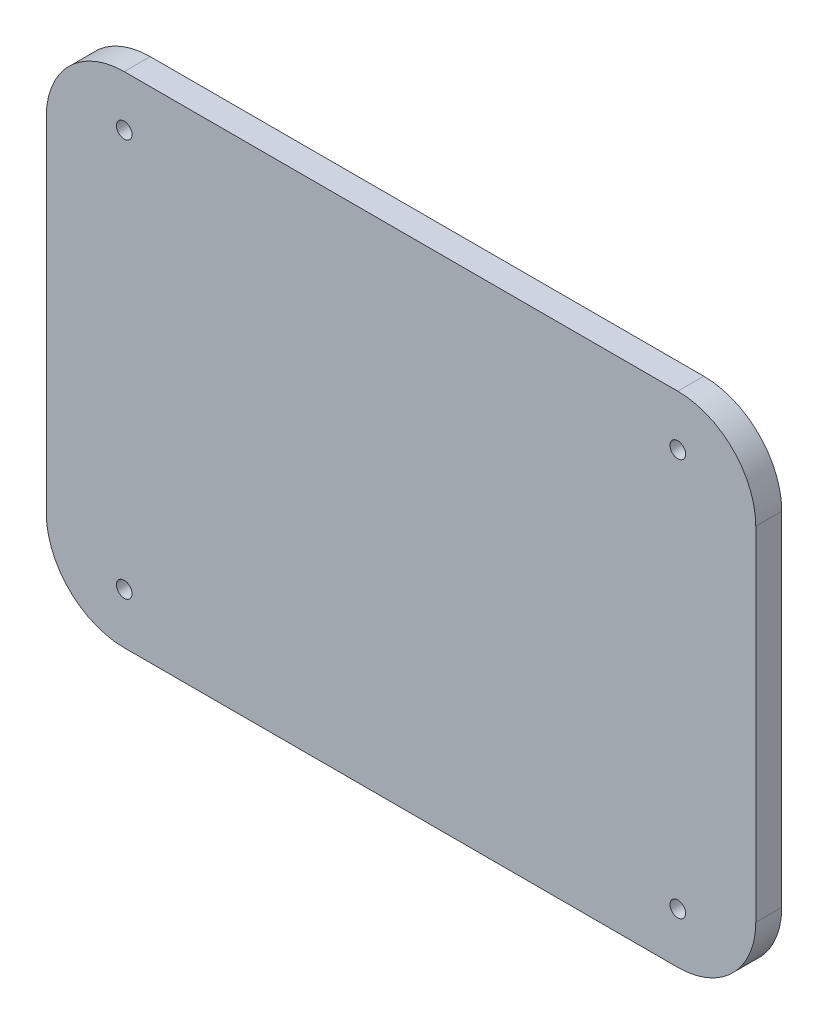
SolidWorks part; units mm, degrees
material "Acrylic (Medium-high impact)"
ref_plane "Front Plane" through (0, 0, 0) normal (0, 0, 1) x (1, 0, 0)
ref_plane "Top Plane" through (0, 0, 0) normal (0, 1, 0) x (1, 0, 0)
ref_plane "Right Plane" through (0, 0, 0) normal (1, 0, 0) x (0, 0, -1)
sketch "Model" plane through (0, 0, 0) normal (0, 0, 1) x (1, 0, 0)
  line L0 (836.1886, 1132.0702) -> (835.7887, 1132.0702)
  line L1 (836.1886, 1132.0702) -> (835.7887, 1132.0702)
  line L2 (836.5018, 1132.0643) -> (836.1886, 1132.0702)
  line L3 (836.5018, 1132.0643) -> (836.1886, 1132.0702)
  line L4 (836.7677, 1132.0446) -> (836.5018, 1132.0643)
  line L5 (836.7677, 1132.0446) -> (836.5018, 1132.0643)
  line L6 (836.9883, 1132.0111) -> (836.7677, 1132.0446)
  line L7 (836.9883, 1132.0111) -> (836.7677, 1132.0446)
  line L8 (837.1636, 1131.9638) -> (836.9883, 1132.0111)
  line L9 (837.1636, 1131.9638) -> (836.9883, 1132.0111)
  line L10 (837.3133, 1131.9008) -> (837.1636, 1131.9638)
  line L11 (837.3133, 1131.9008) -> (837.1636, 1131.9638)
  line L12 (837.4611, 1131.8141) -> (837.3133, 1131.9008)
  line L13 (837.4611, 1131.8141) -> (837.3133, 1131.9008)
  line L14 (837.6029, 1131.7077) -> (837.4611, 1131.8141)
  line L15 (837.6029, 1131.7077) -> (837.4611, 1131.8141)
  line L16 (837.7408, 1131.5777) -> (837.6029, 1131.7077)
  line L17 (837.7408, 1131.5777) -> (837.6029, 1131.7077)
  line L18 (837.8156, 1131.495) -> (837.7408, 1131.5777)
  line L19 (837.8156, 1131.495) -> (837.7408, 1131.5777)
  line L20 (837.9082, 1131.3847) -> (837.8156, 1131.495)
  line L21 (837.9082, 1131.3847) -> (837.8156, 1131.495)
  line L22 (838.0146, 1131.2468) -> (837.9082, 1131.3847)
  line L23 (838.0146, 1131.2468) -> (837.9082, 1131.3847)
  line L24 (838.1367, 1131.0833) -> (838.0146, 1131.2468)
  line L25 (838.1367, 1131.0833) -> (838.0146, 1131.2468)
  line L26 (838.2746, 1130.8903) -> (838.1367, 1131.0833)
  line L27 (838.2746, 1130.8903) -> (838.1367, 1131.0833)
  line L28 (838.4262, 1130.6716) -> (838.2746, 1130.8903)
  line L29 (838.4262, 1130.6716) -> (838.2746, 1130.8903)
  line L30 (838.5956, 1130.4254) -> (838.4262, 1130.6716)
  line L31 (838.5956, 1130.4254) -> (838.4262, 1130.6716)
  line L32 (838.7788, 1130.1516) -> (838.5956, 1130.4254)
  line L33 (838.7788, 1130.1516) -> (838.5956, 1130.4254)
  line L34 (840.1971, 1128.0361) -> (838.7788, 1130.1516)
  line L35 (840.1971, 1128.0361) -> (838.7788, 1130.1516)
  line L36 (842.5963, 1128.0361) -> (840.1971, 1128.0361)
  line L37 (842.5963, 1128.0361) -> (840.1971, 1128.0361)
  line L38 (841.4104, 1129.9369) -> (842.5963, 1128.0361)
  line L39 (841.4104, 1129.9369) -> (842.5963, 1128.0361)
  line L40 (841.2371, 1130.2127) -> (841.4104, 1129.9369)
  line L41 (841.2371, 1130.2127) -> (841.4104, 1129.9369)
  line L42 (841.0716, 1130.4648) -> (841.2371, 1130.2127)
  line L43 (841.0716, 1130.4648) -> (841.2371, 1130.2127)
  line L44 (840.916, 1130.6953) -> (841.0716, 1130.4648)
  line L45 (840.916, 1130.6953) -> (841.0716, 1130.4648)
  line L46 (840.7703, 1130.9041) -> (840.916, 1130.6953)
  line L47 (840.7703, 1130.9041) -> (840.916, 1130.6953)
  line L48 (840.6324, 1131.0892) -> (840.7703, 1130.9041)
  line L49 (840.6324, 1131.0892) -> (840.7703, 1130.9041)
  line L50 (840.5044, 1131.2527) -> (840.6324, 1131.0892)
  line L51 (840.5044, 1131.2527) -> (840.6324, 1131.0892)
  line L52 (840.3862, 1131.3945) -> (840.5044, 1131.2527)
  line L53 (840.3862, 1131.3945) -> (840.5044, 1131.2527)
  line L54 (840.2759, 1131.5147) -> (840.3862, 1131.3945)
  line L55 (840.2759, 1131.5147) -> (840.3862, 1131.3945)
  line L56 (840.0513, 1131.7274) -> (840.2759, 1131.5147)
  line L57 (840.0513, 1131.7274) -> (840.2759, 1131.5147)
  line L58 (839.8011, 1131.9323) -> (840.0513, 1131.7274)
  line L59 (839.8011, 1131.9323) -> (840.0513, 1131.7274)
  line L60 (839.5214, 1132.1273) -> (839.8011, 1131.9323)
  line L61 (839.5214, 1132.1273) -> (839.8011, 1131.9323)
  line L62 (839.2142, 1132.3144) -> (839.5214, 1132.1273)
  line L63 (839.2142, 1132.3144) -> (839.5214, 1132.1273)
  line L64 (839.5195, 1132.3676) -> (839.2142, 1132.3144)
  line L65 (839.5195, 1132.3676) -> (839.2142, 1132.3144)
  line L66 (839.8071, 1132.4365) -> (839.5195, 1132.3676)
  line L67 (839.8071, 1132.4365) -> (839.5195, 1132.3676)
  line L68 (840.0769, 1132.5212) -> (839.8071, 1132.4365)
  line L69 (840.0769, 1132.5212) -> (839.8071, 1132.4365)
  line L70 (840.329, 1132.6237) -> (840.0769, 1132.5212)
  line L71 (840.329, 1132.6237) -> (840.0769, 1132.5212)
  line L72 (840.5634, 1132.7399) -> (840.329, 1132.6237)
  line L73 (840.5634, 1132.7399) -> (840.329, 1132.6237)
  line L74 (840.7782, 1132.8738) -> (840.5634, 1132.7399)
  line L75 (840.7782, 1132.8738) -> (840.5634, 1132.7399)
  line L76 (840.9771, 1133.0235) -> (840.7782, 1132.8738)
  line L77 (840.9771, 1133.0235) -> (840.7782, 1132.8738)
  line L78 (841.1563, 1133.189) -> (840.9771, 1133.0235)
  line L79 (841.1563, 1133.189) -> (840.9771, 1133.0235)
  line L80 (841.3159, 1133.3702) -> (841.1563, 1133.189)
  line L81 (841.3159, 1133.3702) -> (841.1563, 1133.189)
  line L82 (841.4558, 1133.5652) -> (841.3159, 1133.3702)
  line L83 (841.4558, 1133.5652) -> (841.3159, 1133.3702)
  line L84 (841.572, 1133.774) -> (841.4558, 1133.5652)
  line L85 (841.572, 1133.774) -> (841.4558, 1133.5652)
  line L86 (841.6685, 1133.9966) -> (841.572, 1133.774)
  line L87 (841.6685, 1133.9966) -> (841.572, 1133.774)
  line L88 (841.7433, 1134.233) -> (841.6685, 1133.9966)
  line L89 (841.7433, 1134.233) -> (841.6685, 1133.9966)
  line L90 (841.7965, 1134.4831) -> (841.7433, 1134.233)
  line L91 (841.7965, 1134.4831) -> (841.7433, 1134.233)
  line L92 (841.83, 1134.7471) -> (841.7965, 1134.4831)
  line L93 (841.83, 1134.7471) -> (841.7965, 1134.4831)
  line L94 (841.8399, 1135.0248) -> (841.83, 1134.7471)
  line L95 (841.8399, 1135.0248) -> (841.83, 1134.7471)
  line L96 (841.832, 1135.2454) -> (841.8399, 1135.0248)
  line L97 (841.832, 1135.2454) -> (841.8399, 1135.0248)
  line L98 (841.8123, 1135.4601) -> (841.832, 1135.2454)
  line L99 (841.8123, 1135.4601) -> (841.832, 1135.2454)
  line L100 (841.7768, 1135.665) -> (841.8123, 1135.4601)
  line L101 (841.7768, 1135.665) -> (841.8123, 1135.4601)
  line L102 (841.7296, 1135.8639) -> (841.7768, 1135.665)
  line L103 (841.7296, 1135.8639) -> (841.7768, 1135.665)
  line L104 (841.6665, 1136.053) -> (841.7296, 1135.8639)
  line L105 (841.6665, 1136.053) -> (841.7296, 1135.8639)
  line L106 (841.5897, 1136.2343) -> (841.6665, 1136.053)
  line L107 (841.5897, 1136.2343) -> (841.6665, 1136.053)
  line L108 (841.5011, 1136.4076) -> (841.5897, 1136.2343)
  line L109 (841.5011, 1136.4076) -> (841.5897, 1136.2343)
  line L110 (841.3967, 1136.5731) -> (841.5011, 1136.4076)
  line L111 (841.3967, 1136.5731) -> (841.5011, 1136.4076)
  line L112 (841.1603, 1136.8725) -> (841.3967, 1136.5731)
  line L113 (841.1603, 1136.8725) -> (841.3967, 1136.5731)
  line L114 (840.8924, 1137.1226) -> (841.1603, 1136.8725)
  line L115 (840.8924, 1137.1226) -> (841.1603, 1136.8725)
  line L116 (840.593, 1137.3255) -> (840.8924, 1137.1226)
  line L117 (840.593, 1137.3255) -> (840.8924, 1137.1226)
  line L118 (840.264, 1137.4811) -> (840.593, 1137.3255)
  line L119 (840.264, 1137.4811) -> (840.593, 1137.3255)
  line L120 (840.0769, 1137.5422) -> (840.264, 1137.4811)
  line L121 (840.0769, 1137.5422) -> (840.264, 1137.4811)
  line L122 (839.8622, 1137.5954) -> (840.0769, 1137.5422)
  line L123 (839.8622, 1137.5954) -> (840.0769, 1137.5422)
  line L124 (839.618, 1137.6407) -> (839.8622, 1137.5954)
  line L125 (839.618, 1137.6407) -> (839.8622, 1137.5954)
  line L126 (839.3442, 1137.6781) -> (839.618, 1137.6407)
  line L127 (839.3442, 1137.6781) -> (839.618, 1137.6407)
  line L128 (839.0428, 1137.7057) -> (839.3442, 1137.6781)
  line L129 (839.0428, 1137.7057) -> (839.3442, 1137.6781)
  line L130 (838.7119, 1137.7274) -> (839.0428, 1137.7057)
  line L131 (838.7119, 1137.7274) -> (839.0428, 1137.7057)
  line L132 (838.3534, 1137.7392) -> (838.7119, 1137.7274)
  line L133 (838.3534, 1137.7392) -> (838.7119, 1137.7274)
  line L134 (837.9653, 1137.7431) -> (838.3534, 1137.7392)
  line L135 (837.9653, 1137.7431) -> (838.3534, 1137.7392)
  line L136 (833.7717, 1137.7431) -> (837.9653, 1137.7431)
  line L137 (833.7717, 1137.7431) -> (837.9653, 1137.7431)
  line L138 (833.7717, 1128.0361) -> (833.7717, 1137.7431)
  line L139 (833.7717, 1128.0361) -> (833.7717, 1137.7431)
  line L140 (835.7887, 1128.0361) -> (833.7717, 1128.0361)
  line L141 (835.7887, 1128.0361) -> (833.7717, 1128.0361)
  line L142 (835.7887, 1132.0702) -> (835.7887, 1128.0361)
  line L143 (835.7887, 1132.0702) -> (835.7887, 1128.0361)
  line L144 (851.3546, 1130.1792) -> (847.4801, 1130.1792)
  line L145 (851.3546, 1130.1792) -> (847.4801, 1130.1792)
  line L146 (852.1406, 1128.0361) -> (851.3546, 1130.1792)
  line L147 (852.1406, 1128.0361) -> (851.3546, 1130.1792)
  line L148 (854.396, 1128.0361) -> (852.1406, 1128.0361)
  line L149 (854.396, 1128.0361) -> (852.1406, 1128.0361)
  line L150 (850.6948, 1137.7431) -> (854.396, 1128.0361)
  line L151 (850.6948, 1137.7431) -> (854.396, 1128.0361)
  line L152 (848.138, 1137.7431) -> (850.6948, 1137.7431)
  line L153 (848.138, 1137.7431) -> (850.6948, 1137.7431)
  line L154 (844.4368, 1128.0361) -> (848.138, 1137.7431)
  line L155 (844.4368, 1128.0361) -> (848.138, 1137.7431)
  line L156 (846.6922, 1128.0361) -> (844.4368, 1128.0361)
  line L157 (846.6922, 1128.0361) -> (844.4368, 1128.0361)
  line L158 (847.4801, 1130.1792) -> (846.6922, 1128.0361)
  line L159 (847.4801, 1130.1792) -> (846.6922, 1128.0361)
  line L160 (850.4446, 1044.1431) -> (850.4446, 1039.1431)
  line L161 (850.4446, 1044.1431) -> (850.4446, 1039.1431)
  line L162 (825.4446, 1044.1431) -> (850.4446, 1044.1431)
  line L163 (825.4446, 1044.1431) -> (850.4446, 1044.1431)
  line L164 (825.4446, 1039.1431) -> (825.4446, 1044.1431)
  line L165 (825.4446, 1039.1431) -> (825.4446, 1044.1431)
  line L166 (850.4446, 1039.1431) -> (825.4446, 1039.1431)
  line L167 (850.4446, 1039.1431) -> (825.4446, 1039.1431)
  line L168 (822.752, 1129.8246) -> (822.6141, 1130.1575)
  line L169 (822.752, 1129.8246) -> (822.6141, 1130.1575)
  line L170 (822.9155, 1129.5193) -> (822.752, 1129.8246)
  line L171 (822.9155, 1129.5193) -> (822.752, 1129.8246)
  line L172 (823.1026, 1129.2396) -> (822.9155, 1129.5193)
  line L173 (823.1026, 1129.2396) -> (822.9155, 1129.5193)
  line L174 (823.3153, 1128.9875) -> (823.1026, 1129.2396)
  line L175 (823.3153, 1128.9875) -> (823.1026, 1129.2396)
  line L176 (823.5537, 1128.761) -> (823.3153, 1128.9875)
  line L177 (823.5537, 1128.761) -> (823.3153, 1128.9875)
  line L178 (823.8157, 1128.562) -> (823.5537, 1128.761)
  line L179 (823.8157, 1128.562) -> (823.5537, 1128.761)
  line L180 (824.1033, 1128.3887) -> (823.8157, 1128.562)
  line L181 (824.1033, 1128.3887) -> (823.8157, 1128.562)
  line L182 (824.4145, 1128.2429) -> (824.1033, 1128.3887)
  line L183 (824.4145, 1128.2429) -> (824.1033, 1128.3887)
  line L184 (824.7513, 1128.1227) -> (824.4145, 1128.2429)
  line L185 (824.7513, 1128.1227) -> (824.4145, 1128.2429)
  line L186 (825.1137, 1128.0302) -> (824.7513, 1128.1227)
  line L187 (825.1137, 1128.0302) -> (824.7513, 1128.1227)
  line L188 (825.4998, 1127.9632) -> (825.1137, 1128.0302)
  line L189 (825.4998, 1127.9632) -> (825.1137, 1128.0302)
  line L190 (825.9115, 1127.9238) -> (825.4998, 1127.9632)
  line L191 (825.9115, 1127.9238) -> (825.4998, 1127.9632)
  line L192 (826.3488, 1127.91) -> (825.9115, 1127.9238)
  line L193 (826.3488, 1127.91) -> (825.9115, 1127.9238)
  line L194 (826.8393, 1127.9238) -> (826.3488, 1127.91)
  line L195 (826.8393, 1127.9238) -> (826.3488, 1127.91)
  line L196 (827.2982, 1127.9632) -> (826.8393, 1127.9238)
  line L197 (827.2982, 1127.9632) -> (826.8393, 1127.9238)
  line L198 (827.7217, 1128.0282) -> (827.2982, 1127.9632)
  line L199 (827.7217, 1128.0282) -> (827.2982, 1127.9632)
  line L200 (828.1117, 1128.1208) -> (827.7217, 1128.0282)
  line L201 (828.1117, 1128.1208) -> (827.7217, 1128.0282)
  line L202 (828.4683, 1128.239) -> (828.1117, 1128.1208)
  line L203 (828.4683, 1128.239) -> (828.1117, 1128.1208)
  line L204 (828.7913, 1128.3847) -> (828.4683, 1128.239)
  line L205 (828.7913, 1128.3847) -> (828.4683, 1128.239)
  line L206 (829.0809, 1128.5561) -> (828.7913, 1128.3847)
  line L207 (829.0809, 1128.5561) -> (828.7913, 1128.3847)
  line L208 (829.3369, 1128.7531) -> (829.0809, 1128.5561)
  line L209 (829.3369, 1128.7531) -> (829.0809, 1128.5561)
  line L210 (829.5615, 1128.9698) -> (829.3369, 1128.7531)
  line L211 (829.5615, 1128.9698) -> (829.3369, 1128.7531)
  line L212 (829.7545, 1129.2002) -> (829.5615, 1128.9698)
  line L213 (829.7545, 1129.2002) -> (829.5615, 1128.9698)
  line L214 (829.92, 1129.4425) -> (829.7545, 1129.2002)
  line L215 (829.92, 1129.4425) -> (829.7545, 1129.2002)
  line L216 (830.0539, 1129.6966) -> (829.92, 1129.4425)
  line L217 (830.0539, 1129.6966) -> (829.92, 1129.4425)
  line L218 (830.1583, 1129.9625) -> (830.0539, 1129.6966)
  line L219 (830.1583, 1129.9625) -> (830.0539, 1129.6966)
  line L220 (830.2332, 1130.2422) -> (830.1583, 1129.9625)
  line L221 (830.2332, 1130.2422) -> (830.1583, 1129.9625)
  line L222 (830.2765, 1130.5337) -> (830.2332, 1130.2422)
  line L223 (830.2765, 1130.5337) -> (830.2332, 1130.2422)
  line L224 (830.2923, 1130.8371) -> (830.2765, 1130.5337)
  line L225 (830.2923, 1130.8371) -> (830.2765, 1130.5337)
  line L226 (830.2706, 1131.2488) -> (830.2923, 1130.8371)
  line L227 (830.2706, 1131.2488) -> (830.2923, 1130.8371)
  line L228 (830.2036, 1131.6289) -> (830.2706, 1131.2488)
  line L229 (830.2036, 1131.6289) -> (830.2706, 1131.2488)
  line L230 (830.0914, 1131.9776) -> (830.2036, 1131.6289)
  line L231 (830.0914, 1131.9776) -> (830.2036, 1131.6289)
  line L232 (829.9338, 1132.2928) -> (830.0914, 1131.9776)
  line L233 (829.9338, 1132.2928) -> (830.0914, 1131.9776)
  line L234 (829.7348, 1132.5803) -> (829.9338, 1132.2928)
  line L235 (829.7348, 1132.5803) -> (829.9338, 1132.2928)
  line L236 (829.4965, 1132.8384) -> (829.7348, 1132.5803)
  line L237 (829.4965, 1132.8384) -> (829.7348, 1132.5803)
  line L238 (829.2187, 1133.0708) -> (829.4965, 1132.8384)
  line L239 (829.2187, 1133.0708) -> (829.4965, 1132.8384)
  line L240 (828.8996, 1133.2737) -> (829.2187, 1133.0708)
  line L241 (828.8996, 1133.2737) -> (829.2187, 1133.0708)
  line L242 (828.7184, 1133.3682) -> (828.8996, 1133.2737)
  line L243 (828.7184, 1133.3682) -> (828.8996, 1133.2737)
  line L244 (828.5096, 1133.4628) -> (828.7184, 1133.3682)
  line L245 (828.5096, 1133.4628) -> (828.7184, 1133.3682)
  line L246 (828.2772, 1133.5554) -> (828.5096, 1133.4628)
  line L247 (828.2772, 1133.5554) -> (828.5096, 1133.4628)
  line L248 (828.0172, 1133.6499) -> (828.2772, 1133.5554)
  line L249 (828.0172, 1133.6499) -> (828.2772, 1133.5554)
  line L250 (827.7316, 1133.7405) -> (828.0172, 1133.6499)
  line L251 (827.7316, 1133.7405) -> (828.0172, 1133.6499)
  line L252 (827.4203, 1133.8331) -> (827.7316, 1133.7405)
  line L253 (827.4203, 1133.8331) -> (827.7316, 1133.7405)
  line L254 (827.0835, 1133.9237) -> (827.4203, 1133.8331)
  line L255 (827.0835, 1133.9237) -> (827.4203, 1133.8331)
  line L256 (826.7211, 1134.0143) -> (827.0835, 1133.9237)
  line L257 (826.7211, 1134.0143) -> (827.0835, 1133.9237)
  line L258 (826.3823, 1134.0971) -> (826.7211, 1134.0143)
  line L259 (826.3823, 1134.0971) -> (826.7211, 1134.0143)
  line L260 (826.073, 1134.1778) -> (826.3823, 1134.0971)
  line L261 (826.073, 1134.1778) -> (826.3823, 1134.0971)
  line L262 (825.7973, 1134.2566) -> (826.073, 1134.1778)
  line L263 (825.7973, 1134.2566) -> (826.073, 1134.1778)
  line L264 (825.555, 1134.3334) -> (825.7973, 1134.2566)
  line L265 (825.555, 1134.3334) -> (825.7973, 1134.2566)
  line L266 (825.3422, 1134.4083) -> (825.555, 1134.3334)
  line L267 (825.3422, 1134.4083) -> (825.555, 1134.3334)
  line L268 (825.161, 1134.4792) -> (825.3422, 1134.4083)
  line L269 (825.161, 1134.4792) -> (825.3422, 1134.4083)
  line L270 (825.0133, 1134.5501) -> (825.161, 1134.4792)
  line L271 (825.0133, 1134.5501) -> (825.161, 1134.4792)
  line L272 (824.8971, 1134.6191) -> (825.0133, 1134.5501)
  line L273 (824.8971, 1134.6191) -> (825.0133, 1134.5501)
  line L274 (824.7198, 1134.7628) -> (824.8971, 1134.6191)
  line L275 (824.7198, 1134.7628) -> (824.8971, 1134.6191)
  line L276 (824.5937, 1134.9224) -> (824.7198, 1134.7628)
  line L277 (824.5937, 1134.9224) -> (824.7198, 1134.7628)
  line L278 (824.5189, 1135.0957) -> (824.5937, 1134.9224)
  line L279 (824.5189, 1135.0957) -> (824.5937, 1134.9224)
  line L280 (824.4933, 1135.2868) -> (824.5189, 1135.0957)
  line L281 (824.4933, 1135.2868) -> (824.5189, 1135.0957)
  line L282 (824.5011, 1135.3853) -> (824.4933, 1135.2868)
  line L283 (824.5011, 1135.3853) -> (824.4933, 1135.2868)
  line L284 (824.5228, 1135.4798) -> (824.5011, 1135.3853)
  line L285 (824.5228, 1135.4798) -> (824.5011, 1135.3853)
  line L286 (824.5583, 1135.5705) -> (824.5228, 1135.4798)
  line L287 (824.5583, 1135.5705) -> (824.5228, 1135.4798)
  line L288 (824.6075, 1135.6552) -> (824.5583, 1135.5705)
  line L289 (824.6075, 1135.6552) -> (824.5583, 1135.5705)
  line L290 (824.6725, 1135.7379) -> (824.6075, 1135.6552)
  line L291 (824.6725, 1135.7379) -> (824.6075, 1135.6552)
  line L292 (824.7513, 1135.8147) -> (824.6725, 1135.7379)
  line L293 (824.7513, 1135.8147) -> (824.6725, 1135.7379)
  line L294 (824.8439, 1135.8896) -> (824.7513, 1135.8147)
  line L295 (824.8439, 1135.8896) -> (824.7513, 1135.8147)
  line L296 (824.9503, 1135.9585) -> (824.8439, 1135.8896)
  line L297 (824.9503, 1135.9585) -> (824.8439, 1135.8896)
  line L298 (825.0704, 1136.0215) -> (824.9503, 1135.9585)
  line L299 (825.0704, 1136.0215) -> (824.9503, 1135.9585)
  line L300 (825.2024, 1136.0767) -> (825.0704, 1136.0215)
  line L301 (825.2024, 1136.0767) -> (825.0704, 1136.0215)
  line L302 (825.3481, 1136.124) -> (825.2024, 1136.0767)
  line L303 (825.3481, 1136.124) -> (825.2024, 1136.0767)
  line L304 (825.5038, 1136.1634) -> (825.3481, 1136.124)
  line L305 (825.5038, 1136.1634) -> (825.3481, 1136.124)
  line L306 (825.6732, 1136.1929) -> (825.5038, 1136.1634)
  line L307 (825.6732, 1136.1929) -> (825.5038, 1136.1634)
  line L308 (825.8544, 1136.2126) -> (825.6732, 1136.1929)
  line L309 (825.8544, 1136.2126) -> (825.6732, 1136.1929)
  line L310 (826.0474, 1136.2264) -> (825.8544, 1136.2126)
  line L311 (826.0474, 1136.2264) -> (825.8544, 1136.2126)
  line L312 (826.2523, 1136.2303) -> (826.0474, 1136.2264)
  line L313 (826.2523, 1136.2303) -> (826.0474, 1136.2264)
  line L314 (826.4571, 1136.2264) -> (826.2523, 1136.2303)
  line L315 (826.4571, 1136.2264) -> (826.2523, 1136.2303)
  line L316 (826.6502, 1136.2106) -> (826.4571, 1136.2264)
  line L317 (826.6502, 1136.2106) -> (826.4571, 1136.2264)
  line L318 (826.8314, 1136.187) -> (826.6502, 1136.2106)
  line L319 (826.8314, 1136.187) -> (826.6502, 1136.2106)
  line L320 (827.0008, 1136.1535) -> (826.8314, 1136.187)
  line L321 (827.0008, 1136.1535) -> (826.8314, 1136.187)
  line L322 (827.1564, 1136.1102) -> (827.0008, 1136.1535)
  line L323 (827.1564, 1136.1102) -> (827.0008, 1136.1535)
  line L324 (827.3022, 1136.057) -> (827.1564, 1136.1102)
  line L325 (827.3022, 1136.057) -> (827.1564, 1136.1102)
  line L326 (827.4341, 1135.9959) -> (827.3022, 1136.057)
  line L327 (827.4341, 1135.9959) -> (827.3022, 1136.057)
  line L328 (827.5543, 1135.923) -> (827.4341, 1135.9959)
  line L329 (827.5543, 1135.923) -> (827.4341, 1135.9959)
  line L330 (827.6626, 1135.8383) -> (827.5543, 1135.923)
  line L331 (827.6626, 1135.8383) -> (827.5543, 1135.923)
  line L332 (827.7631, 1135.7399) -> (827.6626, 1135.8383)
  line L333 (827.7631, 1135.7399) -> (827.6626, 1135.8383)
  line L334 (827.8517, 1135.6276) -> (827.7631, 1135.7399)
  line L335 (827.8517, 1135.6276) -> (827.7631, 1135.7399)
  line L336 (827.9325, 1135.4995) -> (827.8517, 1135.6276)
  line L337 (827.9325, 1135.4995) -> (827.8517, 1135.6276)
  line L338 (828.0014, 1135.3577) -> (827.9325, 1135.4995)
  line L339 (828.0014, 1135.3577) -> (827.9325, 1135.4995)
  line L340 (828.0605, 1135.2001) -> (828.0014, 1135.3577)
  line L341 (828.0605, 1135.2001) -> (828.0014, 1135.3577)
  line L342 (828.1098, 1135.0288) -> (828.0605, 1135.2001)
  line L343 (828.1098, 1135.0288) -> (828.0605, 1135.2001)
  line L344 (828.1492, 1134.8436) -> (828.1098, 1135.0288)
  line L345 (828.1492, 1134.8436) -> (828.1098, 1135.0288)
  line L346 (830.0401, 1134.9697) -> (828.1492, 1134.8436)
  line L347 (830.0401, 1134.9697) -> (828.1492, 1134.8436)
  line L348 (830.0106, 1135.3085) -> (830.0401, 1134.9697)
  line L349 (830.0106, 1135.3085) -> (830.0401, 1134.9697)
  line L350 (829.9535, 1135.6276) -> (830.0106, 1135.3085)
  line L351 (829.9535, 1135.6276) -> (830.0106, 1135.3085)
  line L352 (829.8668, 1135.927) -> (829.9535, 1135.6276)
  line L353 (829.8668, 1135.927) -> (829.9535, 1135.6276)
  line L354 (829.7506, 1136.2047) -> (829.8668, 1135.927)
  line L355 (829.7506, 1136.2047) -> (829.8668, 1135.927)
  line L356 (829.6068, 1136.4628) -> (829.7506, 1136.2047)
  line L357 (829.6068, 1136.4628) -> (829.7506, 1136.2047)
  line L358 (829.4335, 1136.7011) -> (829.6068, 1136.4628)
  line L359 (829.4335, 1136.7011) -> (829.6068, 1136.4628)
  line L360 (829.2306, 1136.9197) -> (829.4335, 1136.7011)
  line L361 (829.2306, 1136.9197) -> (829.4335, 1136.7011)
  line L362 (828.9981, 1137.1167) -> (829.2306, 1136.9197)
  line L363 (828.9981, 1137.1167) -> (829.2306, 1136.9197)
  line L364 (828.7401, 1137.294) -> (828.9981, 1137.1167)
  line L365 (828.7401, 1137.294) -> (828.9981, 1137.1167)
  line L366 (828.4584, 1137.4457) -> (828.7401, 1137.294)
  line L367 (828.4584, 1137.4457) -> (828.7401, 1137.294)
  line L368 (828.1511, 1137.5757) -> (828.4584, 1137.4457)
  line L369 (828.1511, 1137.5757) -> (828.4584, 1137.4457)
  line L370 (827.8202, 1137.682) -> (828.1511, 1137.5757)
  line L371 (827.8202, 1137.682) -> (828.1511, 1137.5757)
  line L372 (827.4657, 1137.7628) -> (827.8202, 1137.682)
  line L373 (827.4657, 1137.7628) -> (827.8202, 1137.682)
  line L374 (827.0875, 1137.8219) -> (827.4657, 1137.7628)
  line L375 (827.0875, 1137.8219) -> (827.4657, 1137.7628)
  line L376 (826.6856, 1137.8574) -> (827.0875, 1137.8219)
  line L377 (826.6856, 1137.8574) -> (827.0875, 1137.8219)
  line L378 (826.2582, 1137.8692) -> (826.6856, 1137.8574)
  line L379 (826.2582, 1137.8692) -> (826.6856, 1137.8574)
  line L380 (825.9726, 1137.8633) -> (826.2582, 1137.8692)
  line L381 (825.9726, 1137.8633) -> (826.2582, 1137.8692)
  line L382 (825.6988, 1137.8495) -> (825.9726, 1137.8633)
  line L383 (825.6988, 1137.8495) -> (825.9726, 1137.8633)
  line L384 (825.4368, 1137.8239) -> (825.6988, 1137.8495)
  line L385 (825.4368, 1137.8239) -> (825.6988, 1137.8495)
  line L386 (825.1847, 1137.7884) -> (825.4368, 1137.8239)
  line L387 (825.1847, 1137.7884) -> (825.4368, 1137.8239)
  line L388 (824.9463, 1137.7431) -> (825.1847, 1137.7884)
  line L389 (824.9463, 1137.7431) -> (825.1847, 1137.7884)
  line L390 (824.7178, 1137.688) -> (824.9463, 1137.7431)
  line L391 (824.7178, 1137.688) -> (824.9463, 1137.7431)
  line L392 (824.5031, 1137.623) -> (824.7178, 1137.688)
  line L393 (824.5031, 1137.623) -> (824.7178, 1137.688)
  line L394 (824.2983, 1137.5481) -> (824.5031, 1137.623)
  line L395 (824.2983, 1137.5481) -> (824.5031, 1137.623)
  line L396 (823.922, 1137.3689) -> (824.2983, 1137.5481)
  line L397 (823.922, 1137.3689) -> (824.2983, 1137.5481)
  line L398 (823.5911, 1137.1522) -> (823.922, 1137.3689)
  line L399 (823.5911, 1137.1522) -> (823.922, 1137.3689)
  line L400 (823.2996, 1136.8961) -> (823.5911, 1137.1522)
  line L401 (823.2996, 1136.8961) -> (823.5911, 1137.1522)
  line L402 (823.0534, 1136.6006) -> (823.2996, 1136.8961)
  line L403 (823.0534, 1136.6006) -> (823.2996, 1136.8961)
  line L404 (822.947, 1136.4411) -> (823.0534, 1136.6006)
  line L405 (822.947, 1136.4411) -> (823.0534, 1136.6006)
  line L406 (822.8564, 1136.2776) -> (822.947, 1136.4411)
  line L407 (822.8564, 1136.2776) -> (822.947, 1136.4411)
  line L408 (822.7776, 1136.1082) -> (822.8564, 1136.2776)
  line L409 (822.7776, 1136.1082) -> (822.8564, 1136.2776)
  line L410 (822.7146, 1135.9329) -> (822.7776, 1136.1082)
  line L411 (822.7146, 1135.9329) -> (822.7776, 1136.1082)
  line L412 (822.6653, 1135.7536) -> (822.7146, 1135.9329)
  line L413 (822.6653, 1135.7536) -> (822.7146, 1135.9329)
  line L414 (822.6299, 1135.5705) -> (822.6653, 1135.7536)
  line L415 (822.6299, 1135.5705) -> (822.6653, 1135.7536)
  line L416 (822.6102, 1135.3814) -> (822.6299, 1135.5705)
  line L417 (822.6102, 1135.3814) -> (822.6299, 1135.5705)
  line L418 (822.6023, 1135.1883) -> (822.6102, 1135.3814)
  line L419 (822.6023, 1135.1883) -> (822.6102, 1135.3814)
  line L420 (822.624, 1134.8574) -> (822.6023, 1135.1883)
  line L421 (822.624, 1134.8574) -> (822.6023, 1135.1883)
  line L422 (822.6909, 1134.5363) -> (822.624, 1134.8574)
  line L423 (822.6909, 1134.5363) -> (822.624, 1134.8574)
  line L424 (822.7993, 1134.2271) -> (822.6909, 1134.5363)
  line L425 (822.7993, 1134.2271) -> (822.6909, 1134.5363)
  line L426 (822.9529, 1133.9277) -> (822.7993, 1134.2271)
  line L427 (822.9529, 1133.9277) -> (822.7993, 1134.2271)
  line L428 (823.144, 1133.6499) -> (822.9529, 1133.9277)
  line L429 (823.144, 1133.6499) -> (822.9529, 1133.9277)
  line L430 (823.3646, 1133.3998) -> (823.144, 1133.6499)
  line L431 (823.3646, 1133.3998) -> (823.144, 1133.6499)
  line L432 (823.6148, 1133.1772) -> (823.3646, 1133.3998)
  line L433 (823.6148, 1133.1772) -> (823.3646, 1133.3998)
  line L434 (823.8964, 1132.9822) -> (823.6148, 1133.1772)
  line L435 (823.8964, 1132.9822) -> (823.6148, 1133.1772)
  line L436 (824.056, 1132.8935) -> (823.8964, 1132.9822)
  line L437 (824.056, 1132.8935) -> (823.8964, 1132.9822)
  line L438 (824.2352, 1132.8069) -> (824.056, 1132.8935)
  line L439 (824.2352, 1132.8069) -> (824.056, 1132.8935)
  line L440 (824.4381, 1132.7202) -> (824.2352, 1132.8069)
  line L441 (824.4381, 1132.7202) -> (824.2352, 1132.8069)
  line L442 (824.6607, 1132.6375) -> (824.4381, 1132.7202)
  line L443 (824.6607, 1132.6375) -> (824.4381, 1132.7202)
  line L444 (824.905, 1132.5547) -> (824.6607, 1132.6375)
  line L445 (824.905, 1132.5547) -> (824.6607, 1132.6375)
  line L446 (825.1709, 1132.4759) -> (824.905, 1132.5547)
  line L447 (825.1709, 1132.4759) -> (824.905, 1132.5547)
  line L448 (825.4585, 1132.3972) -> (825.1709, 1132.4759)
  line L449 (825.4585, 1132.3972) -> (825.1709, 1132.4759)
  line L450 (825.7677, 1132.3203) -> (825.4585, 1132.3972)
  line L451 (825.7677, 1132.3203) -> (825.4585, 1132.3972)
  line L452 (826.1085, 1132.2376) -> (825.7677, 1132.3203)
  line L453 (826.1085, 1132.2376) -> (825.7677, 1132.3203)
  line L454 (826.4177, 1132.1627) -> (826.1085, 1132.2376)
  line L455 (826.4177, 1132.1627) -> (826.1085, 1132.2376)
  line L456 (826.6935, 1132.0918) -> (826.4177, 1132.1627)
  line L457 (826.6935, 1132.0918) -> (826.4177, 1132.1627)
  line L458 (826.9397, 1132.0268) -> (826.6935, 1132.0918)
  line L459 (826.9397, 1132.0268) -> (826.6935, 1132.0918)
  line L460 (827.1525, 1131.9697) -> (826.9397, 1132.0268)
  line L461 (827.1525, 1131.9697) -> (826.9397, 1132.0268)
  line L462 (827.3337, 1131.9165) -> (827.1525, 1131.9697)
  line L463 (827.3337, 1131.9165) -> (827.1525, 1131.9697)
  line L464 (827.4814, 1131.8712) -> (827.3337, 1131.9165)
  line L465 (827.4814, 1131.8712) -> (827.3337, 1131.9165)
  line L466 (827.5996, 1131.8299) -> (827.4814, 1131.8712)
  line L467 (827.5996, 1131.8299) -> (827.4814, 1131.8712)
  line L468 (827.7887, 1131.7491) -> (827.5996, 1131.8299)
  line L469 (827.7887, 1131.7491) -> (827.5996, 1131.8299)
  line L470 (827.9542, 1131.6585) -> (827.7887, 1131.7491)
  line L471 (827.9542, 1131.6585) -> (827.7887, 1131.7491)
  line L472 (828.0901, 1131.558) -> (827.9542, 1131.6585)
  line L473 (828.0901, 1131.558) -> (827.9542, 1131.6585)
  line L474 (828.2023, 1131.4458) -> (828.0901, 1131.558)
  line L475 (828.2023, 1131.4458) -> (828.0901, 1131.558)
  line L476 (828.289, 1131.3236) -> (828.2023, 1131.4458)
  line L477 (828.289, 1131.3236) -> (828.2023, 1131.4458)
  line L478 (828.352, 1131.1877) -> (828.289, 1131.3236)
  line L479 (828.352, 1131.1877) -> (828.289, 1131.3236)
  line L480 (828.3895, 1131.04) -> (828.352, 1131.1877)
  line L481 (828.3895, 1131.04) -> (828.352, 1131.1877)
  line L482 (828.4013, 1130.8804) -> (828.3895, 1131.04)
  line L483 (828.4013, 1130.8804) -> (828.3895, 1131.04)
  line L484 (828.3934, 1130.7425) -> (828.4013, 1130.8804)
  line L485 (828.3934, 1130.7425) -> (828.4013, 1130.8804)
  line L486 (828.3678, 1130.6086) -> (828.3934, 1130.7425)
  line L487 (828.3678, 1130.6086) -> (828.3934, 1130.7425)
  line L488 (828.3264, 1130.4825) -> (828.3678, 1130.6086)
  line L489 (828.3264, 1130.4825) -> (828.3678, 1130.6086)
  line L490 (828.2693, 1130.3604) -> (828.3264, 1130.4825)
  line L491 (828.2693, 1130.3604) -> (828.3264, 1130.4825)
  line L492 (828.1964, 1130.2442) -> (828.2693, 1130.3604)
  line L493 (828.1964, 1130.2442) -> (828.2693, 1130.3604)
  line L494 (828.1058, 1130.1339) -> (828.1964, 1130.2442)
  line L495 (828.1058, 1130.1339) -> (828.1964, 1130.2442)
  line L496 (827.9995, 1130.0295) -> (828.1058, 1130.1339)
  line L497 (827.9995, 1130.0295) -> (828.1058, 1130.1339)
  line L498 (827.8754, 1129.931) -> (827.9995, 1130.0295)
  line L499 (827.8754, 1129.931) -> (827.9995, 1130.0295)
  line L500 (827.7375, 1129.8424) -> (827.8754, 1129.931)
  line L501 (827.7375, 1129.8424) -> (827.8754, 1129.931)
  line L502 (827.5878, 1129.7636) -> (827.7375, 1129.8424)
  line L503 (827.5878, 1129.7636) -> (827.7375, 1129.8424)
  line L504 (827.4263, 1129.6986) -> (827.5878, 1129.7636)
  line L505 (827.4263, 1129.6986) -> (827.5878, 1129.7636)
  line L506 (827.2509, 1129.6454) -> (827.4263, 1129.6986)
  line L507 (827.2509, 1129.6454) -> (827.4263, 1129.6986)
  line L508 (827.0638, 1129.602) -> (827.2509, 1129.6454)
  line L509 (827.0638, 1129.602) -> (827.2509, 1129.6454)
  line L510 (826.8649, 1129.5725) -> (827.0638, 1129.602)
  line L511 (826.8649, 1129.5725) -> (827.0638, 1129.602)
  line L512 (826.6541, 1129.5548) -> (826.8649, 1129.5725)
  line L513 (826.6541, 1129.5548) -> (826.8649, 1129.5725)
  line L514 (826.4296, 1129.5489) -> (826.6541, 1129.5548)
  line L515 (826.4296, 1129.5489) -> (826.6541, 1129.5548)
  line L516 (826.203, 1129.5567) -> (826.4296, 1129.5489)
  line L517 (826.203, 1129.5567) -> (826.4296, 1129.5489)
  line L518 (825.9903, 1129.5784) -> (826.203, 1129.5567)
  line L519 (825.9903, 1129.5784) -> (826.203, 1129.5567)
  line L520 (825.7874, 1129.6158) -> (825.9903, 1129.5784)
  line L521 (825.7874, 1129.6158) -> (825.9903, 1129.5784)
  line L522 (825.5983, 1129.667) -> (825.7874, 1129.6158)
  line L523 (825.5983, 1129.667) -> (825.7874, 1129.6158)
  line L524 (825.4191, 1129.734) -> (825.5983, 1129.667)
  line L525 (825.4191, 1129.734) -> (825.5983, 1129.667)
  line L526 (825.2536, 1129.8148) -> (825.4191, 1129.734)
  line L527 (825.2536, 1129.8148) -> (825.4191, 1129.734)
  line L528 (825.098, 1129.9113) -> (825.2536, 1129.8148)
  line L529 (825.098, 1129.9113) -> (825.2536, 1129.8148)
  line L530 (824.9562, 1130.0216) -> (825.098, 1129.9113)
  line L531 (824.9562, 1130.0216) -> (825.098, 1129.9113)
  line L532 (824.8242, 1130.1477) -> (824.9562, 1130.0216)
  line L533 (824.8242, 1130.1477) -> (824.9562, 1130.0216)
  line L534 (824.706, 1130.2875) -> (824.8242, 1130.1477)
  line L535 (824.706, 1130.2875) -> (824.8242, 1130.1477)
  line L536 (824.5996, 1130.4431) -> (824.706, 1130.2875)
  line L537 (824.5996, 1130.4431) -> (824.706, 1130.2875)
  line L538 (824.5031, 1130.6125) -> (824.5996, 1130.4431)
  line L539 (824.5031, 1130.6125) -> (824.5996, 1130.4431)
  line L540 (824.4204, 1130.7977) -> (824.5031, 1130.6125)
  line L541 (824.4204, 1130.7977) -> (824.5031, 1130.6125)
  line L542 (824.3495, 1130.9966) -> (824.4204, 1130.7977)
  line L543 (824.3495, 1130.9966) -> (824.4204, 1130.7977)
  line L544 (824.2884, 1131.2113) -> (824.3495, 1130.9966)
  line L545 (824.2884, 1131.2113) -> (824.3495, 1130.9966)
  line L546 (824.2411, 1131.4398) -> (824.2884, 1131.2113)
  line L547 (824.2411, 1131.4398) -> (824.2884, 1131.2113)
  line L548 (822.3502, 1131.3138) -> (824.2411, 1131.4398)
  line L549 (822.3502, 1131.3138) -> (824.2411, 1131.4398)
  line L550 (822.4132, 1130.9021) -> (822.3502, 1131.3138)
  line L551 (822.4132, 1130.9021) -> (822.3502, 1131.3138)
  line L552 (822.5018, 1130.516) -> (822.4132, 1130.9021)
  line L553 (822.5018, 1130.516) -> (822.4132, 1130.9021)
  line L554 (822.6141, 1130.1575) -> (822.5018, 1130.516)
  line L555 (822.6141, 1130.1575) -> (822.5018, 1130.516)
  line L556 (845.4446, 1019.1431) -> (830.4446, 1019.1431)
  line L557 (830.4446, 1019.1431) -> (845.4446, 1019.1431)
  line L558 (845.4446, 1009.1431) -> (830.4446, 1009.1431)
  line L559 (845.4446, 1009.1431) -> (830.4446, 1009.1431)
  line L560 (769.6946, 1084.1431) -> (769.6946, 1018.1431)
  line L561 (769.6946, 1084.1431) -> (769.6946, 1018.1431)
  line L562 (784.6946, 1099.1431) -> (792.9446, 1099.1431)
  line L563 (792.9446, 1099.1431) -> (784.6946, 1099.1431)
  line L564 (807.9446, 1128.1431) -> (807.9446, 1114.1431)
  line L565 (807.9446, 1128.1431) -> (807.9446, 1114.1431)
  line L566 (822.9446, 1143.1431) -> (852.9446, 1143.1431)
  line L567 (852.9446, 1143.1431) -> (822.9446, 1143.1431)
  line L568 (867.9446, 1128.1431) -> (867.9446, 1114.1431)
  line L569 (867.9446, 1114.1431) -> (867.9446, 1128.1431)
  line L570 (891.1946, 1099.1431) -> (882.9446, 1099.1431)
  line L571 (891.1946, 1099.1431) -> (882.9446, 1099.1431)
  line L572 (906.1946, 1084.1431) -> (906.1946, 1018.1431)
  line L573 (906.1946, 1018.1431) -> (906.1946, 1084.1431)
  line L574 (891.1946, 1003.1431) -> (784.6946, 1003.1431)
  line L575 (784.6946, 1003.1431) -> (891.1946, 1003.1431)
  line L576 (891.1946, 1099.1431) -> (882.9446, 1099.1431)
  line L577 (826.6541, 1129.5548) -> (826.8649, 1129.5725)
  line L578 (825.098, 1129.9113) -> (825.2536, 1129.8148)
  line L579 (824.2884, 1131.2113) -> (824.3495, 1130.9966)
  line L580 (824.2411, 1131.4398) -> (824.2884, 1131.2113)
  line L581 (891.1946, 1003.1431) -> (784.6946, 1003.1431)
  line L582 (845.4446, 1009.1431) -> (830.4446, 1009.1431)
  line L583 (826.203, 1129.5567) -> (826.4296, 1129.5489)
  line L584 (826.4296, 1129.5489) -> (826.6541, 1129.5548)
  line L585 (825.9903, 1129.5784) -> (826.203, 1129.5567)
  line L586 (824.4204, 1130.7977) -> (824.5031, 1130.6125)
  line L587 (825.4191, 1129.734) -> (825.5983, 1129.667)
  line L588 (826.8649, 1129.5725) -> (827.0638, 1129.602)
  line L589 (824.8242, 1130.1477) -> (824.9562, 1130.0216)
  line L590 (845.4446, 1019.1431) -> (830.4446, 1019.1431)
  line L591 (784.6946, 1099.1431) -> (792.9446, 1099.1431)
  line L592 (827.7887, 1131.7491) -> (827.5996, 1131.8299)
  line L593 (826.4177, 1132.1627) -> (826.1085, 1132.2376)
  line L594 (822.6023, 1135.1883) -> (822.6102, 1135.3814)
  line L595 (823.3646, 1133.3998) -> (823.144, 1133.6499)
  line L596 (824.056, 1132.8935) -> (823.8964, 1132.9822)
  line L597 (828.289, 1131.3236) -> (828.2023, 1131.4458)
  line L598 (825.7677, 1132.3203) -> (825.4585, 1132.3972)
  line L599 (822.6653, 1135.7536) -> (822.7146, 1135.9329)
  line L600 (824.5031, 1130.6125) -> (824.5996, 1130.4431)
  line L601 (822.7993, 1134.2271) -> (822.6909, 1134.5363)
  line L602 (827.9995, 1130.0295) -> (828.1058, 1130.1339)
  line L603 (825.5983, 1129.667) -> (825.7874, 1129.6158)
  line L604 (825.1709, 1132.4759) -> (824.905, 1132.5547)
  line L605 (827.8754, 1129.931) -> (827.9995, 1130.0295)
  line L606 (828.0901, 1131.558) -> (827.9542, 1131.6585)
  line L607 (827.0638, 1129.602) -> (827.2509, 1129.6454)
  line L608 (822.947, 1136.4411) -> (823.0534, 1136.6006)
  line L609 (824.2352, 1132.8069) -> (824.056, 1132.8935)
  line L610 (827.5996, 1131.8299) -> (827.4814, 1131.8712)
  line L611 (824.5996, 1130.4431) -> (824.706, 1130.2875)
  line L612 (824.706, 1130.2875) -> (824.8242, 1130.1477)
  line L613 (828.352, 1131.1877) -> (828.289, 1131.3236)
  line L614 (823.5911, 1137.1522) -> (823.922, 1137.3689)
  line L615 (823.144, 1133.6499) -> (822.9529, 1133.9277)
  line L616 (823.8964, 1132.9822) -> (823.6148, 1133.1772)
  line L617 (822.9529, 1133.9277) -> (822.7993, 1134.2271)
  line L618 (824.4381, 1132.7202) -> (824.2352, 1132.8069)
  line L619 (824.7178, 1137.688) -> (824.9463, 1137.7431)
  line L620 (828.3678, 1130.6086) -> (828.3934, 1130.7425)
  line L621 (826.6935, 1132.0918) -> (826.4177, 1132.1627)
  line L622 (825.2536, 1129.8148) -> (825.4191, 1129.734)
  line L623 (822.3502, 1131.3138) -> (824.2411, 1131.4398)
  line L624 (906.1946, 1084.1431) -> (906.1946, 1018.1431)
  line L625 (826.1085, 1132.2376) -> (825.7677, 1132.3203)
  line L626 (824.2983, 1137.5481) -> (824.5031, 1137.623)
  line L627 (824.5031, 1137.623) -> (824.7178, 1137.688)
  line L628 (823.2996, 1136.8961) -> (823.5911, 1137.1522)
  line L629 (823.922, 1137.3689) -> (824.2983, 1137.5481)
  line L630 (827.3337, 1131.9165) -> (827.1525, 1131.9697)
  line L631 (828.3934, 1130.7425) -> (828.4013, 1130.8804)
  line L632 (828.2693, 1130.3604) -> (828.3264, 1130.4825)
  line L633 (824.9463, 1137.7431) -> (825.1847, 1137.7884)
  line L634 (828.2023, 1131.4458) -> (828.0901, 1131.558)
  line L635 (827.2509, 1129.6454) -> (827.4263, 1129.6986)
  line L636 (827.4814, 1131.8712) -> (827.3337, 1131.9165)
  line L637 (769.6946, 1084.1431) -> (769.6946, 1018.1431)
  line L638 (824.3495, 1130.9966) -> (824.4204, 1130.7977)
  line L639 (824.9562, 1130.0216) -> (825.098, 1129.9113)
  line L640 (825.1847, 1137.7884) -> (825.4368, 1137.8239)
  line L641 (825.4585, 1132.3972) -> (825.1709, 1132.4759)
  line L642 (824.6607, 1132.6375) -> (824.4381, 1132.7202)
  line L643 (825.4368, 1137.8239) -> (825.6988, 1137.8495)
  line L644 (827.7375, 1129.8424) -> (827.8754, 1129.931)
  line L645 (827.9542, 1131.6585) -> (827.7887, 1131.7491)
  line L646 (825.6988, 1137.8495) -> (825.9726, 1137.8633)
  line L647 (822.6102, 1135.3814) -> (822.6299, 1135.5705)
  line L648 (825.7874, 1129.6158) -> (825.9903, 1129.5784)
  line L649 (823.6148, 1133.1772) -> (823.3646, 1133.3998)
  line L650 (824.9503, 1135.9585) -> (824.8439, 1135.8896)
  line L651 (828.0014, 1135.3577) -> (827.9325, 1135.4995)
  line L652 (822.6909, 1134.5363) -> (822.624, 1134.8574)
  line L653 (824.8971, 1134.6191) -> (825.0133, 1134.5501)
  line L654 (827.0835, 1133.9237) -> (827.4203, 1133.8331)
  line L655 (830.0106, 1135.3085) -> (830.0401, 1134.9697)
  line L656 (828.1511, 1137.5757) -> (828.4584, 1137.4457)
  line L657 (825.5038, 1136.1634) -> (825.3481, 1136.124)
  line L658 (827.1564, 1136.1102) -> (827.0008, 1136.1535)
  line L659 (827.5878, 1129.7636) -> (827.7375, 1129.8424)
  line L660 (829.9535, 1135.6276) -> (830.0106, 1135.3085)
  line L661 (822.6299, 1135.5705) -> (822.6653, 1135.7536)
  line L662 (828.1964, 1130.2442) -> (828.2693, 1130.3604)
  line L663 (827.1525, 1131.9697) -> (826.9397, 1132.0268)
  line L664 (828.1058, 1130.1339) -> (828.1964, 1130.2442)
  line L665 (826.8314, 1136.187) -> (826.6502, 1136.2106)
  line L666 (828.1492, 1134.8436) -> (828.1098, 1135.0288)
  line L667 (825.555, 1134.3334) -> (825.7973, 1134.2566)
  line L668 (827.8202, 1137.682) -> (828.1511, 1137.5757)
  line L669 (825.161, 1134.4792) -> (825.3422, 1134.4083)
  line L670 (826.2523, 1136.2303) -> (826.0474, 1136.2264)
  line L671 (826.0474, 1136.2264) -> (825.8544, 1136.2126)
  line L672 (826.2582, 1137.8692) -> (826.6856, 1137.8574)
  line L673 (824.905, 1132.5547) -> (824.6607, 1132.6375)
  line L674 (828.3264, 1130.4825) -> (828.3678, 1130.6086)
  line L675 (827.5543, 1135.923) -> (827.4341, 1135.9959)
  line L676 (822.7776, 1136.1082) -> (822.8564, 1136.2776)
  line L677 (826.073, 1134.1778) -> (826.3823, 1134.0971)
  line L678 (828.3895, 1131.04) -> (828.352, 1131.1877)
  line L679 (827.8517, 1135.6276) -> (827.7631, 1135.7399)
  line L680 (828.1098, 1135.0288) -> (828.0605, 1135.2001)
  line L681 (824.6075, 1135.6552) -> (824.5583, 1135.5705)
  line L682 (822.7146, 1135.9329) -> (822.7776, 1136.1082)
  line L683 (825.0133, 1134.5501) -> (825.161, 1134.4792)
  line L684 (826.4571, 1136.2264) -> (826.2523, 1136.2303)
  line L685 (824.5228, 1135.4798) -> (824.5011, 1135.3853)
  line L686 (828.9981, 1137.1167) -> (829.2306, 1136.9197)
  line L687 (826.3823, 1134.0971) -> (826.7211, 1134.0143)
  line L688 (827.4657, 1137.7628) -> (827.8202, 1137.682)
  line L689 (827.4263, 1129.6986) -> (827.5878, 1129.7636)
  line L690 (826.9397, 1132.0268) -> (826.6935, 1132.0918)
  line L691 (829.6068, 1136.4628) -> (829.7506, 1136.2047)
  line L692 (823.0534, 1136.6006) -> (823.2996, 1136.8961)
  line L693 (829.4335, 1136.7011) -> (829.6068, 1136.4628)
  line L694 (825.3422, 1134.4083) -> (825.555, 1134.3334)
  line L695 (822.8564, 1136.2776) -> (822.947, 1136.4411)
  line L696 (828.0605, 1135.2001) -> (828.0014, 1135.3577)
  line L697 (822.624, 1134.8574) -> (822.6023, 1135.1883)
  line L698 (827.0008, 1136.1535) -> (826.8314, 1136.187)
  line L699 (825.7973, 1134.2566) -> (826.073, 1134.1778)
  line L700 (825.9726, 1137.8633) -> (826.2582, 1137.8692)
  line L701 (825.6732, 1136.1929) -> (825.5038, 1136.1634)
  line L702 (825.0704, 1136.0215) -> (824.9503, 1135.9585)
  line L703 (824.6725, 1135.7379) -> (824.6075, 1135.6552)
  line L704 (825.2024, 1136.0767) -> (825.0704, 1136.0215)
  line L705 (825.3481, 1136.124) -> (825.2024, 1136.0767)
  line L706 (830.0401, 1134.9697) -> (828.1492, 1134.8436)
  line L707 (824.5937, 1134.9224) -> (824.7198, 1134.7628)
  line L708 (827.9325, 1135.4995) -> (827.8517, 1135.6276)
  line L709 (827.4341, 1135.9959) -> (827.3022, 1136.057)
  line L710 (825.8544, 1136.2126) -> (825.6732, 1136.1929)
  line L711 (828.4013, 1130.8804) -> (828.3895, 1131.04)
  line L712 (827.3022, 1136.057) -> (827.1564, 1136.1102)
  line L713 (826.7211, 1134.0143) -> (827.0835, 1133.9237)
  line L714 (826.6856, 1137.8574) -> (827.0875, 1137.8219)
  line L715 (824.4933, 1135.2868) -> (824.5189, 1135.0957)
  line L716 (829.3369, 1128.7531) -> (829.0809, 1128.5561)
  line L717 (828.5096, 1133.4628) -> (828.7184, 1133.3682)
  line L718 (826.8393, 1127.9238) -> (826.3488, 1127.91)
  line L719 (824.7198, 1134.7628) -> (824.8971, 1134.6191)
  line L720 (830.0539, 1129.6966) -> (829.92, 1129.4425)
  line L721 (824.5583, 1135.5705) -> (824.5228, 1135.4798)
  line L722 (841.3967, 1136.5731) -> (841.5011, 1136.4076)
  line L723 (828.1117, 1128.1208) -> (827.7217, 1128.0282)
  line L724 (838.3534, 1137.7392) -> (838.7119, 1137.7274)
  line L725 (827.7316, 1133.7405) -> (828.0172, 1133.6499)
  line L726 (827.7631, 1135.7399) -> (827.6626, 1135.8383)
  line L727 (824.5011, 1135.3853) -> (824.4933, 1135.2868)
  line L728 (823.1026, 1129.2396) -> (822.9155, 1129.5193)
  line L729 (830.2036, 1131.6289) -> (830.2706, 1131.2488)
  line L730 (829.92, 1129.4425) -> (829.7545, 1129.2002)
  line L731 (824.1033, 1128.3887) -> (823.8157, 1128.562)
  line L732 (829.5615, 1128.9698) -> (829.3369, 1128.7531)
  line L733 (829.7348, 1132.5803) -> (829.9338, 1132.2928)
  line L734 (822.4132, 1130.9021) -> (822.3502, 1131.3138)
  line L735 (830.2332, 1130.2422) -> (830.1583, 1129.9625)
  line L736 (830.2765, 1130.5337) -> (830.2332, 1130.2422)
  line L737 (828.7184, 1133.3682) -> (828.8996, 1133.2737)
  line L738 (826.6502, 1136.2106) -> (826.4571, 1136.2264)
  line L739 (824.7513, 1135.8147) -> (824.6725, 1135.7379)
  line L740 (823.5537, 1128.761) -> (823.3153, 1128.9875)
  line L741 (840.8924, 1137.1226) -> (841.1603, 1136.8725)
  line L742 (829.8668, 1135.927) -> (829.9535, 1135.6276)
  line L743 (829.7545, 1129.2002) -> (829.5615, 1128.9698)
  line L744 (839.8622, 1137.5954) -> (840.0769, 1137.5422)
  line L745 (841.5897, 1136.2343) -> (841.6665, 1136.053)
  line L746 (823.3153, 1128.9875) -> (823.1026, 1129.2396)
  line L747 (830.1583, 1129.9625) -> (830.0539, 1129.6966)
  line L748 (827.4203, 1133.8331) -> (827.7316, 1133.7405)
  line L749 (823.8157, 1128.562) -> (823.5537, 1128.761)
  line L750 (828.8996, 1133.2737) -> (829.2187, 1133.0708)
  line L751 (827.0875, 1137.8219) -> (827.4657, 1137.7628)
  line L752 (840.593, 1137.3255) -> (840.8924, 1137.1226)
  line L753 (829.2306, 1136.9197) -> (829.4335, 1136.7011)
  line L754 (828.4584, 1137.4457) -> (828.7401, 1137.294)
  line L755 (824.5189, 1135.0957) -> (824.5937, 1134.9224)
  line L756 (830.0914, 1131.9776) -> (830.2036, 1131.6289)
  line L757 (837.9653, 1137.7431) -> (838.3534, 1137.7392)
  line L758 (839.3442, 1137.6781) -> (839.618, 1137.6407)
  line L759 (824.7513, 1128.1227) -> (824.4145, 1128.2429)
  line L760 (824.8439, 1135.8896) -> (824.7513, 1135.8147)
  line L761 (828.7401, 1137.294) -> (828.9981, 1137.1167)
  line L762 (825.1137, 1128.0302) -> (824.7513, 1128.1227)
  line L763 (827.2982, 1127.9632) -> (826.8393, 1127.9238)
  line L764 (829.0809, 1128.5561) -> (828.7913, 1128.3847)
  line L765 (829.7506, 1136.2047) -> (829.8668, 1135.927)
  line L766 (827.7217, 1128.0282) -> (827.2982, 1127.9632)
  line L767 (841.1603, 1136.8725) -> (841.3967, 1136.5731)
  line L768 (841.6665, 1136.053) -> (841.7296, 1135.8639)
  line L769 (826.3488, 1127.91) -> (825.9115, 1127.9238)
  line L770 (822.9155, 1129.5193) -> (822.752, 1129.8246)
  line L771 (824.4145, 1128.2429) -> (824.1033, 1128.3887)
  line L772 (822.752, 1129.8246) -> (822.6141, 1130.1575)
  line L773 (839.618, 1137.6407) -> (839.8622, 1137.5954)
  line L774 (833.7717, 1137.7431) -> (837.9653, 1137.7431)
  line L775 (841.5011, 1136.4076) -> (841.5897, 1136.2343)
  line L776 (825.9115, 1127.9238) -> (825.4998, 1127.9632)
  line L777 (827.6626, 1135.8383) -> (827.5543, 1135.923)
  line L778 (837.4611, 1131.8141) -> (837.3133, 1131.9008)
  line L779 (822.6141, 1130.1575) -> (822.5018, 1130.516)
  line L780 (841.7433, 1134.233) -> (841.6685, 1133.9966)
  line L781 (841.572, 1133.774) -> (841.4558, 1133.5652)
  line L782 (837.3133, 1131.9008) -> (837.1636, 1131.9638)
  line L783 (835.7887, 1133.709) -> (837.2207, 1133.709)
  line L784 (838.0717, 1133.7228) -> (838.2962, 1133.7327)
  line L785 (840.264, 1137.4811) -> (840.593, 1137.3255)
  line L786 (837.5339, 1133.711) -> (837.8176, 1133.7149)
  line L787 (841.1563, 1133.189) -> (840.9771, 1133.0235)
  line L788 (841.2371, 1130.2127) -> (841.4104, 1129.9369)
  line L789 (841.3159, 1133.3702) -> (841.1563, 1133.189)
  line L790 (841.83, 1134.7471) -> (841.7965, 1134.4831)
  line L791 (839.5214, 1132.1273) -> (839.8011, 1131.9323)
  line L792 (839.0428, 1137.7057) -> (839.3442, 1137.6781)
  line L793 (828.7913, 1128.3847) -> (828.4683, 1128.239)
  line L794 (838.8931, 1133.8016) -> (839.0645, 1133.8607)
  line L795 (838.1367, 1131.0833) -> (838.0146, 1131.2468)
  line L796 (839.5195, 1132.3676) -> (839.2142, 1132.3144)
  line L797 (838.4262, 1130.6716) -> (838.2746, 1130.8903)
  line L798 (841.7768, 1135.665) -> (841.8123, 1135.4601)
  line L799 (838.5956, 1130.4254) -> (838.4262, 1130.6716)
  line L800 (837.2207, 1133.709) -> (837.5339, 1133.711)
  line L801 (839.8011, 1131.9323) -> (840.0513, 1131.7274)
  line L802 (841.6685, 1133.9966) -> (841.572, 1133.774)
  line L803 (829.9338, 1132.2928) -> (830.0914, 1131.9776)
  line L804 (837.7408, 1131.5777) -> (837.6029, 1131.7077)
  line L805 (836.7677, 1132.0446) -> (836.5018, 1132.0643)
  line L806 (836.9883, 1132.0111) -> (836.7677, 1132.0446)
  line L807 (829.2187, 1133.0708) -> (829.4965, 1132.8384)
  line L808 (825.4998, 1127.9632) -> (825.1137, 1128.0302)
  line L809 (828.0172, 1133.6499) -> (828.2772, 1133.5554)
  line L810 (822.5018, 1130.516) -> (822.4132, 1130.9021)
  line L811 (833.7717, 1128.0361) -> (833.7717, 1137.7431)
  line L812 (841.7296, 1135.8639) -> (841.7768, 1135.665)
  line L813 (838.0146, 1131.2468) -> (837.9082, 1131.3847)
  line L814 (841.4104, 1129.9369) -> (842.5963, 1128.0361)
  line L815 (838.7788, 1130.1516) -> (838.5956, 1130.4254)
  line L816 (840.0513, 1131.7274) -> (840.2759, 1131.5147)
  line L817 (840.7703, 1130.9041) -> (840.916, 1130.6953)
  line L818 (837.1636, 1131.9638) -> (836.9883, 1132.0111)
  line L819 (830.2923, 1130.8371) -> (830.2765, 1130.5337)
  line L820 (838.7119, 1137.7274) -> (839.0428, 1137.7057)
  line L821 (840.0769, 1137.5422) -> (840.264, 1137.4811)
  line L822 (841.832, 1135.2454) -> (841.8399, 1135.0248)
  line L823 (837.9082, 1131.3847) -> (837.8156, 1131.495)
  line L824 (841.8123, 1135.4601) -> (841.832, 1135.2454)
  line L825 (840.3862, 1131.3945) -> (840.5044, 1131.2527)
  line L826 (837.6029, 1131.7077) -> (837.4611, 1131.8141)
  line L827 (840.9771, 1133.0235) -> (840.7782, 1132.8738)
  line L828 (837.8156, 1131.495) -> (837.7408, 1131.5777)
  line L829 (841.0716, 1130.4648) -> (841.2371, 1130.2127)
  line L830 (836.5018, 1132.0643) -> (836.1886, 1132.0702)
  line L831 (830.2706, 1131.2488) -> (830.2923, 1130.8371)
  line L832 (828.4683, 1128.239) -> (828.1117, 1128.1208)
  line L833 (840.5044, 1131.2527) -> (840.6324, 1131.0892)
  line L834 (829.4965, 1132.8384) -> (829.7348, 1132.5803)
  line L835 (840.6324, 1131.0892) -> (840.7703, 1130.9041)
  line L836 (841.7965, 1134.4831) -> (841.7433, 1134.233)
  line L837 (835.7887, 1132.0702) -> (835.7887, 1128.0361)
  line L838 (835.7887, 1128.0361) -> (833.7717, 1128.0361)
  line L839 (842.5963, 1128.0361) -> (840.1971, 1128.0361)
  line L840 (839.2142, 1132.3144) -> (839.5214, 1132.1273)
  line L841 (828.2772, 1133.5554) -> (828.5096, 1133.4628)
  line L842 (837.9446, 1143.1431) -> (852.9446, 1143.1431)
  line L843 (838.1288, 1136.0944) -> (837.8865, 1136.1003)
  line L844 (837.8865, 1136.1003) -> (837.6088, 1136.1023)
  line L845 (839.5707, 1134.3315) -> (839.6416, 1134.5087)
  line L846 (837.9446, 1143.1431) -> (852.9446, 1143.1431)
  line L847 (850.4446, 1039.1431) -> (825.4446, 1039.1431)
  line L848 (844.4368, 1128.0361) -> (848.138, 1137.7431)
  line L849 (838.5208, 1136.0767) -> (838.3415, 1136.0865)
  line L850 (837.3015, 1136.1043) -> (835.7887, 1136.1043)
  line L851 (849.4164, 1135.4562) -> (848.0829, 1131.818)
  line L852 (838.6547, 1133.7602) -> (838.7887, 1133.7799)
  line L853 (839.0645, 1133.8607) -> (839.2181, 1133.9434)
  line L854 (840.329, 1132.6237) -> (840.0769, 1132.5212)
  line L855 (840.916, 1130.6953) -> (841.0716, 1130.4648)
  line L856 (839.0507, 1135.9723) -> (838.8694, 1136.0333)
  line L857 (729.3772, 1165.4098) -> (953.7354, 1165.4098)
  line L858 (847.4801, 1130.1792) -> (846.6922, 1128.0361)
  line L859 (839.6967, 1134.9322) -> (839.683, 1135.147)
  line L860 (839.352, 1135.7832) -> (839.2122, 1135.8876)
  line L861 (851.3546, 1130.1792) -> (847.4801, 1130.1792)
  line L862 (852.1406, 1128.0361) -> (851.3546, 1130.1792)
  line L863 (835.7887, 1136.1043) -> (835.7887, 1133.709)
  line L864 (839.8071, 1132.4365) -> (839.5195, 1132.3676)
  line L865 (825.4446, 1044.1431) -> (850.4446, 1044.1431)
  line L866 (850.6948, 1137.7431) -> (854.396, 1128.0361)
  line L867 (838.6705, 1136.0649) -> (838.5208, 1136.0767)
  line L868 (839.4742, 1134.1778) -> (839.5707, 1134.3315)
  line L869 (840.5634, 1132.7399) -> (840.329, 1132.6237)
  line L870 (837.6088, 1136.1023) -> (837.3015, 1136.1043)
  line L871 (838.7847, 1136.0491) -> (838.6705, 1136.0649)
  line L872 (840.2759, 1131.5147) -> (840.3862, 1131.3945)
  line L873 (840.7782, 1132.8738) -> (840.5634, 1132.7399)
  line L874 (850.4446, 1044.1431) -> (850.4446, 1039.1431)
  line L875 (838.7887, 1133.7799) -> (838.8931, 1133.8016)
  line L876 (839.683, 1135.147) -> (839.6416, 1135.34)
  line L877 (840.1971, 1128.0361) -> (838.7788, 1130.1516)
  line L878 (840.0769, 1132.5212) -> (839.8071, 1132.4365)
  line L879 (729.3772, 966.6577) -> (729.3772, 1165.4098)
  line L880 (838.2746, 1130.8903) -> (838.1367, 1131.0833)
  line L881 (836.1886, 1132.0702) -> (835.7887, 1132.0702)
  line L882 (838.2962, 1133.7327) -> (838.4893, 1133.7445)
  line L883 (953.7354, 966.6577) -> (729.3772, 966.6577)
  line L884 (839.5707, 1135.5094) -> (839.4742, 1135.6571)
  line L885 (838.4893, 1133.7445) -> (838.6547, 1133.7602)
  line L886 (839.4742, 1135.6571) -> (839.352, 1135.7832)
  line L887 (841.4558, 1133.5652) -> (841.3159, 1133.3702)
  line L888 (838.3415, 1136.0865) -> (838.1288, 1136.0944)
  line L889 (953.7354, 1165.4098) -> (953.7354, 966.6577)
  line L890 (848.0829, 1131.818) -> (850.7519, 1131.818)
  line L891 (846.6922, 1128.0361) -> (844.4368, 1128.0361)
  line L892 (841.8399, 1135.0248) -> (841.83, 1134.7471)
  line L893 (838.8694, 1136.0333) -> (838.7847, 1136.0491)
  line L894 (848.138, 1137.7431) -> (850.6948, 1137.7431)
  line L895 (850.7519, 1131.818) -> (849.4164, 1135.4562)
  line L896 (837.8176, 1133.7149) -> (838.0717, 1133.7228)
  line L897 (837.9446, 1143.1431) -> (822.9446, 1143.1431)
  line L898 (854.396, 1128.0361) -> (852.1406, 1128.0361)
  line L899 (839.6416, 1134.5087) -> (839.683, 1134.7077)
  line L900 (825.4446, 1039.1431) -> (825.4446, 1044.1431)
  line L901 (839.683, 1134.7077) -> (839.6967, 1134.9322)
  line L902 (839.354, 1134.0478) -> (839.4742, 1134.1778)
  line L903 (835.7887, 1136.1043) -> (835.7887, 1128.0361)
  line L904 (830.4446, 1014.1431) -> (845.4446, 1014.1431)
  line L905 (837.9446, 1003.1431) -> (837.9446, 1143.1431)
  line L906 (769.6946, 1051.1431) -> (906.1946, 1051.1431)
  line L907 (839.2122, 1135.8876) -> (839.0507, 1135.9723)
  line L908 (839.6416, 1135.34) -> (839.5707, 1135.5094)
  line L909 (867.9446, 1128.1431) -> (867.9446, 1114.1431)
  line L910 (837.9446, 1014.1431) -> (837.9446, 1143.1431)
  line L911 (837.9446, 1014.1431) -> (837.9446, 1003.1431)
  line L912 (839.2181, 1133.9434) -> (839.354, 1134.0478)
  line L913 (833.7717, 1128.0361) -> (833.7717, 1137.7431)
  line L914 (807.9446, 1128.1431) -> (807.9446, 1114.1431)
  circle A0 centre (891.1946, 1012.8931) radius 1.5
  circle A1 centre (891.1946, 1012.8931) radius 1.5
  circle A2 centre (891.1946, 1089.3931) radius 1.5
  circle A3 centre (891.1946, 1089.3931) radius 1.5
  circle A4 centre (866.1437, 1057.9429) radius 1.7
  circle A5 centre (866.1437, 1057.9429) radius 1.7
  circle A6 centre (809.8829, 1057.95) radius 1.7
  circle A7 centre (809.8829, 1057.95) radius 1.7
  circle A8 centre (820.4131, 1082.5088) radius 1.7
  circle A9 centre (820.4131, 1082.5088) radius 1.7
  circle A10 centre (855.4546, 1082.5264) radius 1.7
  circle A11 centre (855.4546, 1082.5264) radius 1.7
  circle A12 centre (784.6946, 1089.3931) radius 1.5
  circle A13 centre (784.6946, 1089.3931) radius 1.5
  circle A14 centre (789.6946, 1044.1431) radius 1.5
  circle A15 centre (789.6946, 1044.1431) radius 1.5
  circle A16 centre (837.9446, 1119.9277) radius 1.5
  circle A17 centre (837.9446, 1119.9277) radius 1.5
  circle A18 centre (886.1946, 1044.1431) radius 1.5
  circle A19 centre (886.1946, 1044.1431) radius 1.5
  circle A20 centre (845.9446, 1054.1431) radius 1.5
  circle A21 centre (845.9446, 1054.1431) radius 1.5
  circle A22 centre (784.6946, 1012.8931) radius 1.5
  circle A23 centre (784.6946, 1012.8931) radius 1.5
  circle A24 centre (789.6946, 1058.1431) radius 1.5
  circle A25 centre (789.6946, 1058.1431) radius 1.5
  circle A26 centre (829.9446, 1054.1431) radius 1.5
  circle A27 centre (829.9446, 1054.1431) radius 1.5
  circle A28 centre (849.9446, 1099.1431) radius 1.5
  circle A29 centre (849.9446, 1099.1431) radius 1.5
  circle A30 centre (825.9446, 1099.1431) radius 1.5
  circle A31 centre (825.9446, 1099.1431) radius 1.5
  circle A32 centre (886.1946, 1058.1431) radius 1.5
  circle A33 centre (886.1946, 1058.1431) radius 1.5
  arc A34 (845.4446, 1009.1431) -> (845.4446, 1019.1431) centre (845.4446, 1014.1431) ccw
  arc A35 (845.4446, 1009.1431) -> (845.4446, 1019.1431) centre (845.4446, 1014.1431) ccw
  arc A36 (830.4446, 1019.1431) -> (830.4446, 1009.1431) centre (830.4446, 1014.1431) ccw
  arc A37 (830.4446, 1019.1431) -> (830.4446, 1009.1431) centre (830.4446, 1014.1431) ccw
  arc A38 (769.6946, 1018.1431) -> (784.6946, 1003.1431) centre (784.6946, 1018.1431) ccw
  arc A39 (769.6946, 1018.1431) -> (784.6946, 1003.1431) centre (784.6946, 1018.1431) ccw
  arc A40 (784.6946, 1099.1431) -> (769.6946, 1084.1431) centre (784.6946, 1084.1431) ccw
  arc A41 (784.6946, 1099.1431) -> (769.6946, 1084.1431) centre (784.6946, 1084.1431) ccw
  arc A42 (792.9446, 1099.1431) -> (807.9446, 1114.1431) centre (792.9446, 1114.1431) ccw
  arc A43 (792.9446, 1099.1431) -> (807.9446, 1114.1431) centre (792.9446, 1114.1431) ccw
  arc A44 (822.9446, 1143.1431) -> (807.9446, 1128.1431) centre (822.9446, 1128.1431) ccw
  arc A45 (822.9446, 1143.1431) -> (807.9446, 1128.1431) centre (822.9446, 1128.1431) ccw
  arc A46 (867.9446, 1128.1431) -> (852.9446, 1143.1431) centre (852.9446, 1128.1431) ccw
  arc A47 (867.9446, 1128.1431) -> (852.9446, 1143.1431) centre (852.9446, 1128.1431) ccw
  arc A48 (867.9446, 1114.1431) -> (882.9446, 1099.1431) centre (882.9446, 1114.1431) ccw
  arc A49 (867.9446, 1114.1431) -> (882.9446, 1099.1431) centre (882.9446, 1114.1431) ccw
  arc A50 (906.1946, 1084.1431) -> (891.1946, 1099.1431) centre (891.1946, 1084.1431) ccw
  arc A51 (906.1946, 1084.1431) -> (891.1946, 1099.1431) centre (891.1946, 1084.1431) ccw
  arc A52 (891.1946, 1003.1431) -> (906.1946, 1018.1431) centre (891.1946, 1018.1431) ccw
  arc A53 (891.1946, 1003.1431) -> (906.1946, 1018.1431) centre (891.1946, 1018.1431) ccw
  circle A54 centre (825.9446, 1099.1431) radius 1.5
  arc A55 (850.4446, 1014.1431) -> (845.4446, 1019.1431) centre (845.4446, 1014.1431) ccw
  arc A56 (845.4446, 1009.1431) -> (850.4446, 1014.1431) centre (845.4446, 1014.1431) ccw
  circle A57 centre (789.6946, 1058.1431) radius 1.5
  circle A58 centre (829.9446, 1054.1431) radius 1.5
  circle A59 centre (849.9446, 1099.1431) radius 1.5
  arc A60 (825.4446, 1014.1431) -> (830.4446, 1009.1431) centre (830.4446, 1014.1431) ccw
  arc A61 (906.1946, 1084.1431) -> (891.1946, 1099.1431) centre (891.1946, 1084.1431) ccw
  circle A62 centre (784.6946, 1012.8931) radius 1.5
  circle A63 centre (886.1946, 1058.1431) radius 1.5
  arc A64 (891.1946, 1003.1431) -> (906.1946, 1018.1431) centre (891.1946, 1018.1431) ccw
  arc A65 (769.6946, 1018.1431) -> (784.6946, 1003.1431) centre (784.6946, 1018.1431) ccw
  circle A66 centre (845.9446, 1054.1431) radius 1.5
  circle A67 centre (837.9446, 1119.9277) radius 1.5
  circle A68 centre (789.6946, 1044.1431) radius 1.5
  arc A69 (830.4446, 1019.1431) -> (825.4446, 1014.1431) centre (830.4446, 1014.1431) ccw
  arc A70 (784.6946, 1099.1431) -> (769.6946, 1084.1431) centre (784.6946, 1084.1431) ccw
  circle A71 centre (886.1946, 1044.1431) radius 1.5
  arc A72 (822.9446, 1143.1431) -> (807.9446, 1128.1431) centre (822.9446, 1128.1431) ccw
  arc A73 (867.9446, 1128.1431) -> (852.9446, 1143.1431) centre (852.9446, 1128.1431) ccw
  arc A74 (867.9446, 1114.1431) -> (882.9446, 1099.1431) centre (882.9446, 1114.1431) ccw
  circle A75 centre (855.4546, 1082.5264) radius 1.7
  circle A76 centre (784.6946, 1089.3931) radius 1.5
  circle A77 centre (891.1946, 1089.3931) radius 1.5
  circle A78 centre (891.1946, 1012.8931) radius 1.5
  circle A79 centre (866.1437, 1057.9429) radius 1.7
  circle A80 centre (809.8829, 1057.95) radius 1.7
  circle A81 centre (820.4131, 1082.5088) radius 1.7
  arc A82 (792.9446, 1099.1431) -> (807.9446, 1114.1431) centre (792.9446, 1114.1431) ccw
  point P425 (0, 0)
sketch "Sketch2" plane through (0, 0, 0) normal (0, 0, 1) x (1, 0, 0)
  line L0 (792.9446, 1099.1431) -> (882.9446, 1099.1431)
  line L1 (891.1946, 1099.1431) -> (882.9446, 1099.1431) construction
  line L2 (906.1946, 1084.1431) -> (906.1946, 1018.1431) construction
  line L3 (891.1946, 1003.1431) -> (784.6946, 1003.1431) construction
  line L4 (769.6946, 1084.1431) -> (769.6946, 1018.1431) construction
  line L5 (784.6946, 1099.1431) -> (792.9446, 1099.1431) construction
  line L6 (891.1946, 1099.1431) -> (882.9446, 1099.1431)
  line L7 (906.1946, 1084.1431) -> (906.1946, 1018.1431)
  line L8 (891.1946, 1003.1431) -> (784.6946, 1003.1431)
  line L9 (769.6946, 1084.1431) -> (769.6946, 1018.1431)
  line L10 (784.6946, 1099.1431) -> (792.9446, 1099.1431)
  circle A0 centre (784.6946, 1089.3931) radius 1.5 construction
  circle A1 centre (784.6946, 1012.8931) radius 1.5 construction
  circle A2 centre (891.1946, 1012.8931) radius 1.5 construction
  circle A3 centre (891.1946, 1089.3931) radius 1.5 construction
  arc A4 (906.1946, 1084.1431) -> (891.1946, 1099.1431) centre (891.1946, 1084.1431) ccw construction
  arc A5 (891.1946, 1003.1431) -> (906.1946, 1018.1431) centre (891.1946, 1018.1431) ccw construction
  arc A6 (769.6946, 1018.1431) -> (784.6946, 1003.1431) centre (784.6946, 1018.1431) ccw construction
  arc A7 (784.6946, 1099.1431) -> (769.6946, 1084.1431) centre (784.6946, 1084.1431) ccw construction
  circle A8 centre (784.6946, 1089.3931) radius 1.5
  circle A9 centre (784.6946, 1012.8931) radius 1.5
  circle A10 centre (891.1946, 1012.8931) radius 1.5
  circle A11 centre (891.1946, 1089.3931) radius 1.5
  arc A12 (906.1946, 1084.1431) -> (891.1946, 1099.1431) centre (891.1946, 1084.1431) ccw
  arc A13 (891.1946, 1003.1431) -> (906.1946, 1018.1431) centre (891.1946, 1018.1431) ccw
  arc A14 (769.6946, 1018.1431) -> (784.6946, 1003.1431) centre (784.6946, 1018.1431) ccw
  arc A15 (784.6946, 1099.1431) -> (769.6946, 1084.1431) centre (784.6946, 1084.1431) ccw
extrude "Boss-Extrude1" add sketch "Sketch2" along normal blind 5
